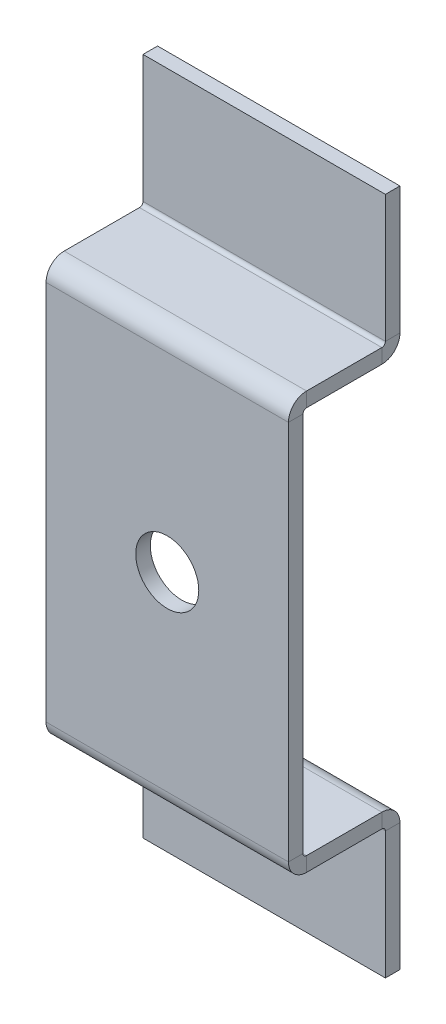
SolidWorks part; units mm, degrees
note: The reader was unsure of these and kept them because the rebuilt part matched: flange length of "边线-法兰1", "边线-法兰2".
ref_plane "前视基准面" through (0, 0, 0) normal (0, 0, 1) x (1, 0, 0)
ref_plane "上视基准面" through (0, 0, 0) normal (0, 1, 0) x (1, 0, 0)
ref_plane "右视基准面" through (0, 0, 0) normal (1, 0, 0) x (0, 0, -1)
other "Configuration Table"
sketch "草图1" plane through (0, 0, 0) normal (0, 0, 1) x (1, 0, 0)
  line L1 (0, 0) -> (50, 0)
  line L2 (0, 0) -> (0, 80)
  line L3 (0, 80) -> (50, 80)
  line L4 (50, 0) -> (50, 80)
  dimension "D1" = 80
  dimension "D2" = 50
base flange "基体-法兰1" sketch "草图1" thickness 3 reverse thickness direction no parameters "D1"=0.7366
edge flange "边线-法兰1" sketch "草图10" flange profiles "草图10", "草图11" flange angle 90 flange length 20 flange position material outside bend radius 0.7366 thickness 3 relief rectangular parameters "D6"=10, "D8"=1
sketch "草图10" plane through (0, 80, -3) normal (0, -1, 0) x (-1, 0, 0)
  line L2 (-50, 0) -> (-50, 17)
  line L3 (-50, 17) -> (0, 17)
  line L4 (0, 17) -> (0, 0)
  line L5 (0, 0) -> (-50, 0) construction
  line L6 (0, 0) -> (-50, 0)
sketch "草图11" plane through (0, 0, -3) normal (0, 1, 0) x (1, 0, 0)
  line L0 (50, 0) -> (0, 0) construction
  line L1 (50, 0) -> (0, 0)
  line L2 (50, 0) -> (50, 17)
  line L3 (50, 17) -> (0, 17)
  line L4 (0, 17) -> (0, 0)
bend "边线折弯1" bend radius 0.7366 bend angle 90 parameters "D5"=1
bend "边线折弯2" bend radius 0.7366 bend angle 90 parameters "D5"=2
edge flange "边线-法兰2" sketch "草图16" flange profiles "草图16", "草图17" flange angle 90 flange length 30 flange position material outside bend radius 0.7366 thickness 3 relief rectangular parameters "D6"=10, "D8"=1
sketch "草图16" plane through (0, -3, -20) normal (0, 0, -1) x (1, 0, 0)
  line L2 (0, 0) -> (0, 27)
  line L3 (0, 27) -> (50, 27)
  line L4 (50, 27) -> (50, 0)
  line L7 (50, 0) -> (0, 0) construction
  line L8 (50, 0) -> (0, 0)
sketch "草图17" plane through (0, 83, -20) normal (0, 0, -1) x (-1, 0, 0)
  line L0 (0, 0) -> (-50, 0) construction
  line L1 (0, 0) -> (-50, 0)
  line L2 (-50, 0) -> (-50, 27)
  line L3 (-50, 27) -> (0, 27)
  line L4 (0, 27) -> (0, 0)
bend "边线折弯3" bend radius 0.7366 bend angle 90 parameters "D5"=3
bend "边线折弯4" bend radius 0.7366 bend angle 90 parameters "D5"=4
sketch "草图18" plane through (0, 0, 0) normal (0, 0, 1) x (1, 0, 0)
  line L7 (50, -30) -> (0, -30) construction
  line L8 (50, 0.7366) -> (50, 79.2634) construction
  circle A0 centre (25, 40) radius 6.5
  dimension "D5" = 13
  dimension "D3" = 70
  dimension "D4" = 25
extrude "切除-拉伸1" cut sketch "草图18" against normal through all normal cut yes
sketch "折弯-线1" plane through (0, 0, 0) normal (0, 1, 0) x (1, 0, 0)
sketch "边界框1" plane through (0, 0, 0) normal (0, 1, 0) x (1, 0, 0)
sheet metal parameters "钣金6" thickness 3 parameters "D1"=0.7366
flat pattern "平板型式6" [suppressed]
sketch "折弯-线2" plane through (0, 0, 0) normal (0, 1, 0) x (1, 0, 0)
sketch "边界框2" [suppressed] plane through (0, 0, 0) normal (0, 1, 0) x (1, 0, 0)
sheet metal parameters "钣金7" thickness 3 parameters "D1"=0.7366
flat pattern "平板型式6" [suppressed]
sketch "折弯-线2" plane through (0, 0, 0) normal (0, 1, 0) x (1, 0, 0)
sketch "边界框2" [suppressed] plane through (0, 0, 0) normal (0, 1, 0) x (1, 0, 0)
bend of the flat pattern "展平-<边线折弯1>1"
bend of the flat pattern "展平-<边线折弯2>1"
sheet metal parameters "钣金8" thickness 3 parameters "D1"=0.7366
flat pattern "平板型式6" [suppressed]
sketch "折弯-线2" plane through (0, 0, 0) normal (0, 1, 0) x (1, 0, 0)
sketch "边界框2" [suppressed] plane through (0, 0, 0) normal (0, 1, 0) x (1, 0, 0)
bend of the flat pattern "展平-<边线折弯1>1"
bend of the flat pattern "展平-<边线折弯2>1"
bend of the flat pattern "展平-<边线折弯3>1"
bend of the flat pattern "展平-<边线折弯4>1"
sheet metal parameters "钣金9" thickness 3 parameters "D1"=0.7366
flat pattern "平板型式6" [suppressed]
sketch "折弯-线2" plane through (0, 0, 0) normal (0, 1, 0) x (1, 0, 0)
sketch "边界框2" [suppressed] plane through (0, 0, 0) normal (0, 1, 0) x (1, 0, 0)
bend of the flat pattern "展平-<边线折弯1>1"
bend of the flat pattern "展平-<边线折弯2>1"
bend of the flat pattern "展平-<边线折弯3>1"
bend of the flat pattern "展平-<边线折弯4>1"
